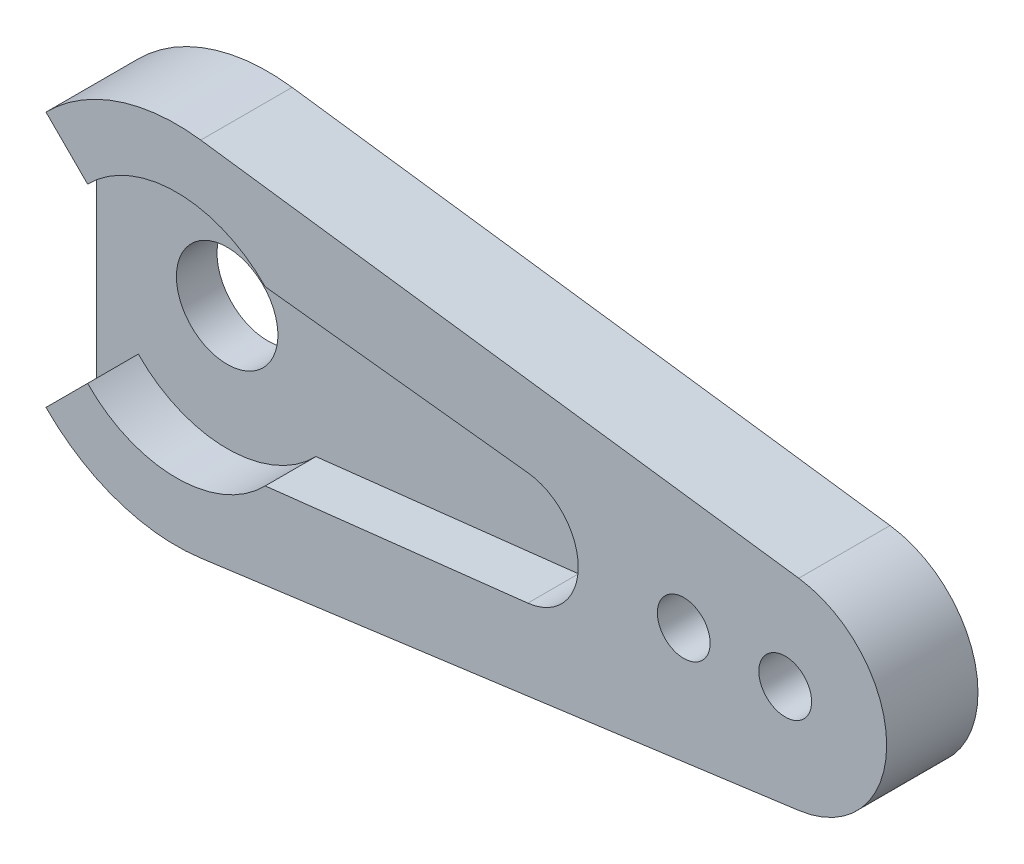
SolidWorks part; units mm, degrees
ref_plane "Front Plane" through (0, 0, 0) normal (0, 0, 1) x (1, 0, 0)
ref_plane "Top Plane" through (0, 0, 0) normal (0, 1, 0) x (1, 0, 0)
ref_plane "Right Plane" through (0, 0, 0) normal (1, 0, 0) x (0, 0, -1)
sketch "Esquisse1" plane through (0, 0, 0) normal (0, 0, 1) x (1, 0, 0)
  line L0 (-4.3758, 4.25) -> (-6.4265, 6.3008)
  line L1 (4.3758, 4.25) -> (17.3156, 2.7822)
  line L2 (17.3156, -2.7822) -> (4.3758, -4.25)
  line L4 (1.2, 8.9196) -> (30.6667, 4.9554)
  line L5 (1.2, -8.9196) -> (30.6667, -4.9554)
  line L6 (-4.3758, -4.25) -> (-6.4265, -6.3008)
  arc A0 (4.3758, 4.25) -> (-4.3758, 4.25) centre (0, 0) ccw
  arc A1 (17.3156, -2.7822) -> (17.3156, 2.7822) centre (17, 0) ccw
  arc A2 (4.3758, -4.25) -> (-4.3758, -4.25) centre (0, 0) cw
  arc A3 (-6.4265, 6.3008) -> (1.2, 8.9196) centre (0, 0) cw
  arc A4 (30.6667, 4.9554) -> (30.6667, -4.9554) centre (30, 0) cw
  arc A5 (-6.4265, -6.3008) -> (1.2, -8.9196) centre (0, 0) ccw
  dimension "D2" = 6.1
  dimension "D3" = 2.8
  dimension "D6" = 9
  dimension "D8" = 5
  dimension "D1" = 8.5
  dimension "D4" = 17
  dimension "D7" = 30
extrude "Main" add sketch "Esquisse1" along normal blind 2.5
sketch "Esquisse2" plane through (0, 0, 0) normal (0, 0, -1) x (-1, 0, 0)
  line L0 (-1.2, -8.9196) -> (-30.6667, -4.9554)
  line L1 (-1.2, -8.9196) -> (-30.6667, -4.9554) construction
  line L3 (-1.2, 8.9196) -> (-30.6667, 4.9554)
  line L4 (6.4265, -6.3008) -> (6.4265, 6.3008)
  arc A0 (-30.6667, 4.9554) -> (-30.6667, -4.9554) centre (-30, 0) ccw construction
  arc A1 (-1.2, -8.9196) -> (6.4265, -6.3008) centre (0, 0) ccw
  circle A2 centre (0, 0) radius 2.5
  arc A3 (6.4265, 6.3008) -> (-1.2, 8.9196) centre (0, 0) ccw
  arc A5 (-30.6667, 4.9554) -> (-30.6667, -4.9554) centre (-30, 0) ccw
  arc A6 (-1.2, -8.9196) -> (6.4265, -6.3008) centre (0, 0) ccw construction
  dimension "D1" = 5
extrude "OriginalBracket" add sketch "Esquisse2" along normal blind 2
sketch "Esquisse3" plane through (0, 0, 2.5) normal (0, 0, 1) x (1, 0, 0)
  circle A0 centre (30, 0) radius 1.3
  arc A2 (30.6667, -4.9554) -> (30.6667, 4.9554) centre (30, 0) ccw construction
  circle A3 centre (25, 0) radius 1.3
  dimension "D1" = 2.6
  dimension "D2" = 5
extrude "FixingHole" cut sketch "Esquisse3" against normal through all
